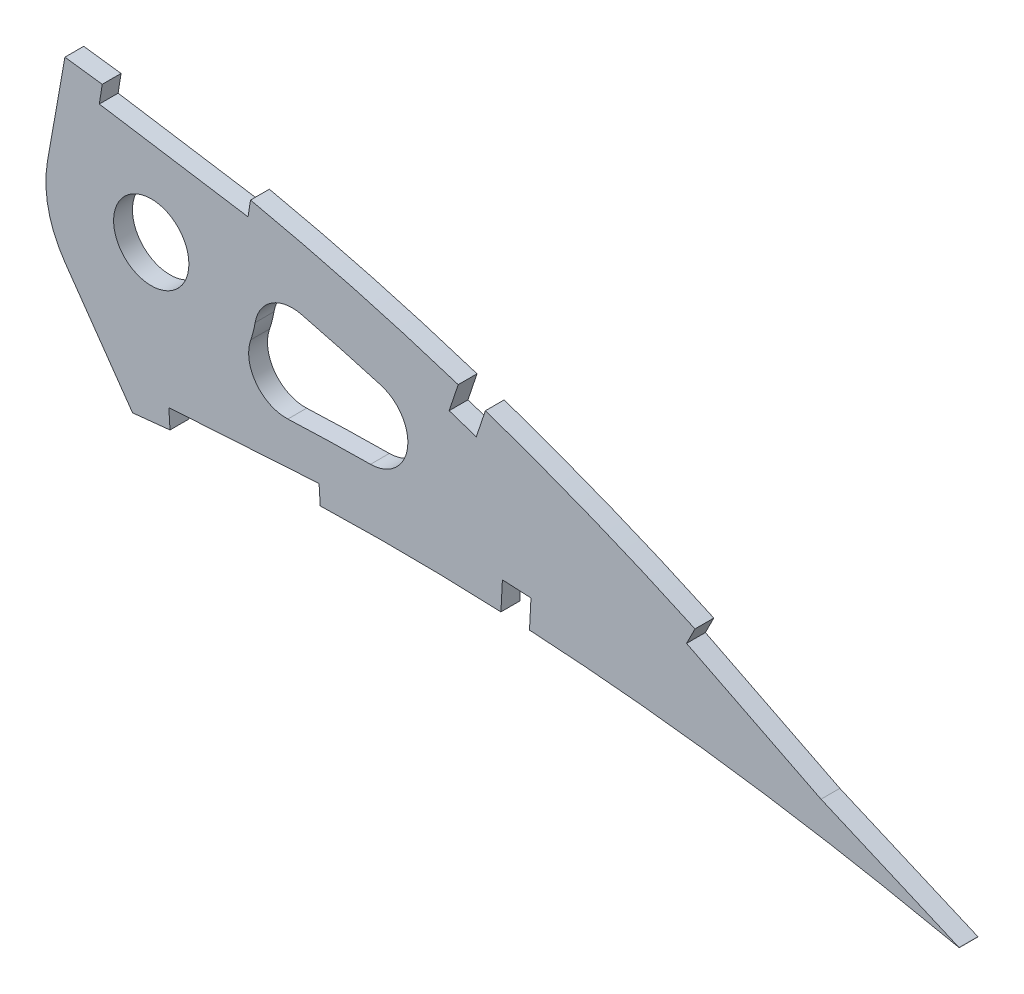
SolidWorks part; units mm, degrees
material "Pine"
ref_plane "Front Plane" through (0, 0, 0) normal (0, 0, 1) x (1, 0, 0)
ref_plane "Top Plane" through (0, 0, 0) normal (0, 1, 0) x (1, 0, 0)
ref_plane "Right Plane" through (0, 0, 0) normal (1, 0, 0) x (0, 0, -1)
curve "Curve1"
  spline degree 3 poles (0, 0, 0) (0.1249, -0.5894, 0) (0.3751, -1.7709, 0) (1.0551, -3.4717, 0) (1.9543, -5.1067, 0) (3.0917, -6.6716, 0) (4.4597, -8.1658, 0) (6.0551, -9.5909, 0) (7.8766, -10.9463, 0) (9.9217, -12.2312, 0) (12.1874, -13.447, 0) (14.6712, -14.593, 0) (17.3708, -15.6688, 0) (20.2833, -16.6729, 0) (23.4051, -17.607, 0) (26.7332, -18.4687, 0) (30.2639, -19.2592, 0) (33.9938, -19.9766, 0) (37.9188, -20.6214, 0) (42.0348, -21.1935, 0) (46.3376, -21.6931, 0) (50.823, -22.1192, 0) (55.4866, -22.4726, 0) (60.3236, -22.7538, 0) (65.3294, -22.9634, 0) (70.4993, -23.1008, 0) (75.828, -23.1681, 0) (81.3109, -23.1662, 0) (86.9426, -23.0948, 0) (92.7182, -22.9577, 0) (98.6323, -22.754, 0) (104.6794, -22.4863, 0) (110.8541, -22.1572, 0) (117.1509, -21.7679, 0) (123.5642, -21.32, 0) (130.0885, -20.8172, 0) (136.7178, -20.2607, 0) (143.4464, -19.6538, 0) (150.2683, -18.9994, 0) (157.1776, -18.2998, 0) (164.1682, -17.5581, 0) (171.2339, -16.7767, 0) (178.3687, -15.9599, 0) (185.566, -15.1091, 0) (192.8198, -14.2292, 0) (200.1233, -13.3218, 0) (207.4703, -12.3905, 0) (214.8542, -11.4396, 0) (222.2681, -10.469, 0) (229.7058, -9.4856, 0) (237.1601, -8.4887, 0) (244.6246, -7.4833, 0) (252.0922, -6.4726, 0) (259.5558, -5.4569, 0) (267.0088, -4.4404, 0) (274.4442, -3.4259, 0) (281.8548, -2.4135, 0) (289.2339, -1.4081, 0) (296.574, -0.4098, 0) (303.8684, 0.5795, 0) (311.1101, 1.5569, 0) (318.2922, 2.521, 0) (325.4074, 3.4714, 0) (332.4485, 4.4082, 0) (339.3029, 5.3032, 0) (345.9529, 6.204, 0) (352.4207, 6.9424, 0) (358.808, 7.5727, 0) (365.1214, 8.0894, 0) (371.3533, 8.5001, 0) (377.4966, 8.8075, 0) (383.544, 9.0161, 0) (389.4878, 9.132, 0) (395.3205, 9.1582, 0) (401.0343, 9.1029, 0) (406.6218, 8.9708, 0) (412.075, 8.7675, 0) (417.3864, 8.5002, 0) (422.5485, 8.1759, 0) (427.5535, 7.7996, 0) (432.3944, 7.38, 0) (437.0637, 6.9232, 0) (441.5544, 6.4344, 0) (445.8598, 5.924, 0) (449.973, 5.3952, 0) (453.8879, 4.8568, 0) (457.5982, 4.3142, 0) (461.0979, 3.7743, 0) (464.3817, 3.2423, 0) (467.4441, 2.7253, 0) (470.2803, 2.228, 0) (472.8856, 1.7553, 0) (475.2562, 1.3133, 0) (477.3874, 0.904, 0) (479.2765, 0.5343, 0) (480.9199, 0.2058, 0) (482.3151, -0.077, 0) (483.4599, -0.3128, 0) (484.3523, -0.4979, 0) (484.9907, -0.6325, 0) (485.3743, -0.7125, 0) (485.5448, -0.7489, 0) (485.5874, -0.758, 0) knots 0 0 0 0 0.003638 0.007293 0.011028 0.014901 0.018963 0.023258 0.027821 0.032679 0.037853 0.043362 0.049215 0.055422 0.061989 0.068918 0.076211 0.083868 0.091887 0.100266 0.109 0.118085 0.127515 0.137285 0.147388 0.157816 0.168563 0.179619 0.190977 0.202627 0.21456 0.226767 0.239236 0.251959 0.264924 0.27812 0.291536 0.30516 0.318981 0.332985 0.347163 0.361499 0.375981 0.390597 0.405333 0.420175 0.43511 0.450124 0.465203 0.480333 0.495501 0.51069 0.525887 0.541078 0.556247 0.571382 0.586466 0.601485 0.616424 0.631269 0.646007 0.660621 0.675098 0.689423 0.703582 0.716908 0.730009 0.742952 0.755726 0.76832 0.780724 0.792927 0.804916 0.816679 0.828204 0.839475 0.850481 0.861208 0.871639 0.881763 0.891564 0.901027 0.910139 0.918884 0.927249 0.935221 0.942785 0.949928 0.956638 0.962904 0.968712 0.974054 0.978918 0.983297 0.98718 0.990561 0.993433 0.995791 0.99763 0.998946 0.999737 1 1 1 1
curve "Curve2"
  spline degree 3 poles (486.1938, 0.758, 0) (486.1565, 0.781, 0) (486.0077, 0.8729, 0) (485.6723, 1.0786, 0) (485.1139, 1.4213, 0) (484.3321, 1.8984, 0) (483.3276, 2.5088, 0) (482.0999, 3.2482, 0) (480.6498, 4.1141, 0) (478.9775, 5.1026, 0) (477.0833, 6.2089, 0) (474.9678, 7.4286, 0) (472.6313, 8.7548, 0) (470.0748, 10.182, 0) (467.2989, 11.7035, 0) (464.3043, 13.3123, 0) (461.0921, 15.0004, 0) (457.6635, 16.7605, 0) (454.019, 18.5827, 0) (450.1605, 20.4596, 0) (446.0892, 22.3819, 0) (441.8065, 24.3391, 0) (437.3149, 26.3234, 0) (432.6155, 28.3224, 0) (427.7112, 30.3274, 0) (422.6039, 32.3272, 0) (417.2967, 34.3124, 0) (411.7916, 36.2703, 0) (406.0928, 38.1924, 0) (400.203, 40.0661, 0) (394.1264, 41.8812, 0) (387.8666, 43.626, 0) (381.4288, 45.2916, 0) (374.8171, 46.8658, 0) (368.037, 48.3381, 0) (361.0939, 49.6996, 0) (353.9938, 50.9366, 0) (346.7562, 52.0484, 0) (339.4976, 52.9732, 0) (332.2539, 53.8802, 0) (325.021, 54.7322, 0) (317.6998, 55.5482, 0) (310.2971, 56.3235, 0) (302.8205, 57.0556, 0) (295.2774, 57.7415, 0) (287.6757, 58.3791, 0) (280.0227, 58.9648, 0) (272.3266, 59.4977, 0) (264.5949, 59.9731, 0) (256.8359, 60.3907, 0) (249.0573, 60.7475, 0) (241.2675, 61.0411, 0) (233.4745, 61.2698, 0) (225.6865, 61.4312, 0) (217.912, 61.5245, 0) (210.159, 61.547, 0) (202.4359, 61.4984, 0) (194.7508, 61.377, 0) (187.1122, 61.1811, 0) (179.5282, 60.9103, 0) (172.0069, 60.5649, 0) (164.5567, 60.1418, 0) (157.1855, 59.6438, 0) (149.9016, 59.0688, 0) (142.713, 58.4167, 0) (135.6273, 57.6901, 0) (128.6522, 56.887, 0) (121.7954, 56.0099, 0) (115.0642, 55.0603, 0) (108.4663, 54.0378, 0) (102.0087, 52.9453, 0) (95.6983, 51.784, 0) (89.542, 50.5572, 0) (83.5463, 49.2652, 0) (77.7176, 47.912, 0) (72.062, 46.4999, 0) (66.5855, 45.0315, 0) (61.2937, 43.5103, 0) (56.192, 41.9397, 0) (51.2862, 40.3215, 0) (46.5802, 38.6618, 0) (42.0796, 36.9619, 0) (37.788, 35.2268, 0) (33.7103, 33.4591, 0) (29.8497, 31.6641, 0) (26.2104, 29.8437, 0) (22.7951, 28.0033, 0) (19.6072, 26.1454, 0) (16.6497, 24.2737, 0) (13.924, 22.3929, 0) (11.4337, 20.504, 0) (9.1798, 18.612, 0) (7.1636, 16.7197, 0) (5.388, 14.8284, 0) (3.8531, 12.9414, 0) (2.5606, 11.0602, 0) (1.511, 9.1866, 0) (0.7066, 7.3219, 0) (0.1466, 5.4673, 0) (-0.16, 3.6254, 0) (-0.2363, 1.7948, 0) (-0.0786, 0.5974, 0) (0, 0, 0) knots 0 0 0 0 0.000254 0.001015 0.002283 0.004057 0.006331 0.009105 0.012374 0.016134 0.02038 0.025106 0.030306 0.035972 0.0421 0.048678 0.055702 0.06316 0.071046 0.07935 0.088063 0.097176 0.106678 0.116562 0.126814 0.137428 0.148394 0.1597 0.171338 0.183298 0.19557 0.208144 0.221012 0.234162 0.247587 0.261277 0.275223 0.289414 0.303771 0.317689 0.331784 0.34604 0.360444 0.374983 0.38964 0.404403 0.419257 0.434187 0.449177 0.464215 0.479284 0.49437 0.509458 0.524532 0.539579 0.554583 0.56953 0.584403 0.599191 0.613877 0.628447 0.642889 0.657186 0.671326 0.685294 0.699078 0.712665 0.726043 0.739198 0.752118 0.764792 0.777208 0.789356 0.801224 0.812804 0.824083 0.835055 0.84571 0.856038 0.866034 0.875689 0.884998 0.893953 0.902553 0.910789 0.918661 0.926166 0.933303 0.940071 0.946475 0.952518 0.958205 0.963547 0.968557 0.97325 0.977651 0.981787 0.985694 0.989415 0.993001 0.996508 1 1 1 1
sketch "Sketch1" plane through (0, 0, 0) normal (0, 0, 1) x (1, 0, 0)
  line L10 (485.5874, -0.758) -> (490.1477, -1.6846)
  line L24 (486.1938, 0.758) -> (490.1477, -1.6846)
  spline S2 degree 3 poles (-3866.8103, -1018.8258) (79.7559, 75.3438) (-9.1933, 22.1629) (1.0551, -3.4717) (1.9543, -5.1067) (3.0917, -6.6716) (4.4597, -8.1658) (6.0551, -9.5909) (7.8766, -10.9463) (9.9217, -12.2312) (12.1874, -13.447) (14.6712, -14.593) (17.3708, -15.6688) (20.2833, -16.6729) (23.4051, -17.607) (26.7332, -18.4687) (30.2639, -19.2592) (33.9938, -19.9766) (37.9188, -20.6214) (42.0348, -21.1935) (46.3376, -21.6931) (50.823, -22.1192) (55.4866, -22.4726) (60.3236, -22.7538) (65.3294, -22.9634) (70.4993, -23.1008) (75.828, -23.1681) (81.3109, -23.1662) (86.9426, -23.0948) (92.7182, -22.9577) (98.6323, -22.754) (104.6794, -22.4863) (110.8541, -22.1572) (117.1509, -21.7679) (123.5642, -21.32) (130.0885, -20.8172) (136.7178, -20.2607) (143.4464, -19.6538) (150.2683, -18.9994) (157.1776, -18.2998) (164.1682, -17.5581) (171.2339, -16.7767) (178.3687, -15.9599) (185.566, -15.1091) (192.8198, -14.2292) (200.1233, -13.3218) (207.4703, -12.3905) (214.8542, -11.4396) (222.2681, -10.469) (229.7058, -9.4856) (237.1601, -8.4887) (244.6246, -7.4833) (252.0922, -6.4726) (259.5558, -5.4569) (267.0088, -4.4404) (274.4442, -3.4259) (281.8548, -2.4135) (289.2339, -1.4081) (296.574, -0.4098) (303.8684, 0.5795) (311.1101, 1.5569) (318.2922, 2.521) (325.4074, 3.4714) (332.4485, 4.4082) (339.3029, 5.3032) (345.9529, 6.204) (352.4207, 6.9424) (358.808, 7.5727) (365.1214, 8.0894) (371.3533, 8.5001) (377.4966, 8.8075) (383.544, 9.0161) (389.4878, 9.132) (395.3205, 9.1582) (401.0343, 9.1029) (406.6218, 8.9708) (412.075, 8.7675) (417.3864, 8.5002) (422.5485, 8.1759) (427.5535, 7.7996) (432.3944, 7.38) (437.0637, 6.9232) (441.5544, 6.4344) (445.8598, 5.924) (449.973, 5.3952) (453.8879, 4.8568) (457.5982, 4.3142) (461.0979, 3.7743) (464.3817, 3.2423) (467.4441, 2.7253) (470.2803, 2.228) (472.8856, 1.7553) (475.2562, 1.3133) (477.3874, 0.904) (479.2765, 0.5343) (480.9199, 0.2058) (482.3151, -0.077) (483.4599, -0.3128) (484.3523, -0.4979) (484.9907, -0.6325) (504.0158, -4.6034) (520.901, -17.6411) (1368.8084, 3899.3631) knots -0.155184 -0.155184 -0.155184 -0.155184 0.003638 0.007293 0.011028 0.014901 0.018963 0.023258 0.027821 0.032679 0.037853 0.043362 0.049215 0.055422 0.061989 0.068918 0.076211 0.083868 0.091887 0.100266 0.109 0.118085 0.127515 0.137285 0.147388 0.157816 0.168563 0.179619 0.190977 0.202627 0.21456 0.226767 0.239236 0.251959 0.264924 0.27812 0.291536 0.30516 0.318981 0.332985 0.347163 0.361499 0.375981 0.390597 0.405333 0.420175 0.43511 0.450124 0.465203 0.480333 0.495501 0.51069 0.525887 0.541078 0.556247 0.571382 0.586466 0.601485 0.616424 0.631269 0.646007 0.660621 0.675098 0.689423 0.703582 0.716908 0.730009 0.742952 0.755726 0.76832 0.780724 0.792927 0.804916 0.816679 0.828204 0.839475 0.850481 0.861208 0.871639 0.881763 0.891564 0.901027 0.910139 0.918884 0.927249 0.935221 0.942785 0.949928 0.956638 0.962904 0.968712 0.974054 0.978918 0.983297 0.98718 0.990561 0.993433 0.995791 0.99763 0.998946 0.999737 1.115177 1.115177 1.115177 1.115177 only from (0, 0) to (485.5874, -0.758) construction
  spline S3 degree 3 poles (2637.6242, 3371.1949) (518.0891, -28.6046) (504.1645, -10.2642) (485.6723, 1.0786) (485.1139, 1.4213) (484.3321, 1.8984) (483.3276, 2.5088) (482.0999, 3.2482) (480.6498, 4.1141) (478.9775, 5.1026) (477.0833, 6.2089) (474.9678, 7.4286) (472.6313, 8.7548) (470.0748, 10.182) (467.2989, 11.7035) (464.3043, 13.3123) (461.0921, 15.0004) (457.6635, 16.7605) (454.019, 18.5827) (450.1605, 20.4596) (446.0892, 22.3819) (441.8065, 24.3391) (437.3149, 26.3234) (432.6155, 28.3224) (427.7112, 30.3274) (422.6039, 32.3272) (417.2967, 34.3124) (411.7916, 36.2703) (406.0928, 38.1924) (400.203, 40.0661) (394.1264, 41.8812) (387.8666, 43.626) (381.4288, 45.2916) (374.8171, 46.8658) (368.037, 48.3381) (361.0939, 49.6996) (353.9938, 50.9366) (346.7562, 52.0484) (339.4976, 52.9732) (332.2539, 53.8802) (325.021, 54.7322) (317.6998, 55.5482) (310.2971, 56.3235) (302.8205, 57.0556) (295.2774, 57.7415) (287.6757, 58.3791) (280.0227, 58.9648) (272.3266, 59.4977) (264.5949, 59.9731) (256.8359, 60.3907) (249.0573, 60.7475) (241.2675, 61.0411) (233.4745, 61.2698) (225.6865, 61.4312) (217.912, 61.5245) (210.159, 61.547) (202.4359, 61.4984) (194.7508, 61.377) (187.1122, 61.1811) (179.5282, 60.9103) (172.0069, 60.5649) (164.5567, 60.1418) (157.1855, 59.6438) (149.9016, 59.0688) (142.713, 58.4167) (135.6273, 57.6901) (128.6522, 56.887) (121.7954, 56.0099) (115.0642, 55.0603) (108.4663, 54.0378) (102.0087, 52.9453) (95.6983, 51.784) (89.542, 50.5572) (83.5463, 49.2652) (77.7176, 47.912) (72.062, 46.4999) (66.5855, 45.0315) (61.2937, 43.5103) (56.192, 41.9397) (51.2862, 40.3215) (46.5802, 38.6618) (42.0796, 36.9619) (37.788, 35.2268) (33.7103, 33.4591) (29.8497, 31.6641) (26.2104, 29.8437) (22.7951, 28.0033) (19.6072, 26.1454) (16.6497, 24.2737) (13.924, 22.3929) (11.4337, 20.504) (9.1798, 18.612) (7.1636, 16.7197) (5.388, 14.8284) (3.8531, 12.9414) (2.5606, 11.0602) (1.511, 9.1866) (0.7066, 7.3219) (0.1466, 5.4673) (-0.16, 3.6254) (-1.3078, -23.9112) (100.477, -44.4073) (-3985.5392, -325.5751) knots -0.123624 -0.123624 -0.123624 -0.123624 0.000254 0.001015 0.002283 0.004057 0.006331 0.009105 0.012374 0.016134 0.02038 0.025106 0.030306 0.035972 0.0421 0.048678 0.055702 0.06316 0.071046 0.07935 0.088063 0.097176 0.106678 0.116562 0.126814 0.137428 0.148394 0.1597 0.171338 0.183298 0.19557 0.208144 0.221012 0.234162 0.247587 0.261277 0.275223 0.289414 0.303771 0.317689 0.331784 0.34604 0.360444 0.374983 0.38964 0.404403 0.419257 0.434187 0.449177 0.464215 0.479284 0.49437 0.509458 0.524532 0.539579 0.554583 0.56953 0.584403 0.599191 0.613877 0.628447 0.642889 0.657186 0.671326 0.685294 0.699078 0.712665 0.726043 0.739198 0.752118 0.764792 0.777208 0.789356 0.801224 0.812804 0.824083 0.835055 0.84571 0.856038 0.866034 0.875689 0.884998 0.893953 0.902553 0.910789 0.918661 0.926166 0.933303 0.940071 0.946475 0.952518 0.958205 0.963547 0.968557 0.97325 0.977651 0.981787 0.985694 0.989415 0.993001 0.996508 1.148636 1.148636 1.148636 1.148636 only from (486.1938, 0.758) to (0, 0) construction
  spline S4 degree 3 poles (0, 0) (0.1249, -0.5894) (0.3751, -1.7709) (1.0551, -3.4717) (1.9543, -5.1067) (3.0917, -6.6716) (4.4597, -8.1658) (6.0551, -9.5909) (7.8766, -10.9463) (9.9217, -12.2312) (12.1874, -13.447) (14.6712, -14.593) (17.3708, -15.6688) (20.2833, -16.6729) (23.4051, -17.607) (26.7332, -18.4687) (30.2639, -19.2592) (33.9938, -19.9766) (37.9188, -20.6214) (42.0348, -21.1935) (46.3376, -21.6931) (50.823, -22.1192) (55.4866, -22.4726) (60.3236, -22.7538) (65.3294, -22.9634) (70.4993, -23.1008) (75.828, -23.1681) (81.3109, -23.1662) (86.9426, -23.0948) (92.7182, -22.9577) (98.6323, -22.754) (104.6794, -22.4863) (110.8541, -22.1572) (117.1509, -21.7679) (123.5642, -21.32) (130.0885, -20.8172) (136.7178, -20.2607) (143.4464, -19.6538) (150.2683, -18.9994) (157.1776, -18.2998) (164.1682, -17.5581) (171.2339, -16.7767) (178.3687, -15.9599) (185.566, -15.1091) (192.8198, -14.2292) (200.1233, -13.3218) (207.4703, -12.3905) (214.8542, -11.4396) (222.2681, -10.469) (229.7058, -9.4856) (237.1601, -8.4887) (244.6246, -7.4833) (252.0922, -6.4726) (259.5558, -5.4569) (267.0088, -4.4404) (274.4442, -3.4259) (281.8548, -2.4135) (289.2339, -1.4081) (296.574, -0.4098) (303.8684, 0.5795) (311.1101, 1.5569) (318.2922, 2.521) (325.4074, 3.4714) (332.4485, 4.4082) (339.3029, 5.3032) (345.9529, 6.204) (352.4207, 6.9424) (358.808, 7.5727) (365.1214, 8.0894) (371.3533, 8.5001) (377.4966, 8.8075) (383.544, 9.0161) (389.4878, 9.132) (395.3205, 9.1582) (401.0343, 9.1029) (406.6218, 8.9708) (412.075, 8.7675) (417.3864, 8.5002) (422.5485, 8.1759) (427.5535, 7.7996) (432.3944, 7.38) (437.0637, 6.9232) (441.5544, 6.4344) (445.8598, 5.924) (449.973, 5.3952) (453.8879, 4.8568) (457.5982, 4.3142) (461.0979, 3.7743) (464.3817, 3.2423) (467.4441, 2.7253) (470.2803, 2.228) (472.8856, 1.7553) (475.2562, 1.3133) (477.3874, 0.904) (479.2765, 0.5343) (480.9199, 0.2058) (482.3151, -0.077) (483.4599, -0.3128) (484.3523, -0.4979) (484.9907, -0.6325) (485.3743, -0.7125) (485.5448, -0.7489) (485.5874, -0.758) knots 0 0 0 0 0.003638 0.007293 0.011028 0.014901 0.018963 0.023258 0.027821 0.032679 0.037853 0.043362 0.049215 0.055422 0.061989 0.068918 0.076211 0.083868 0.091887 0.100266 0.109 0.118085 0.127515 0.137285 0.147388 0.157816 0.168563 0.179619 0.190977 0.202627 0.21456 0.226767 0.239236 0.251959 0.264924 0.27812 0.291536 0.30516 0.318981 0.332985 0.347163 0.361499 0.375981 0.390597 0.405333 0.420175 0.43511 0.450124 0.465203 0.480333 0.495501 0.51069 0.525887 0.541078 0.556247 0.571382 0.586466 0.601485 0.616424 0.631269 0.646007 0.660621 0.675098 0.689423 0.703582 0.716908 0.730009 0.742952 0.755726 0.76832 0.780724 0.792927 0.804916 0.816679 0.828204 0.839475 0.850481 0.861208 0.871639 0.881763 0.891564 0.901027 0.910139 0.918884 0.927249 0.935221 0.942785 0.949928 0.956638 0.962904 0.968712 0.974054 0.978918 0.983297 0.98718 0.990561 0.993433 0.995791 0.99763 0.998946 0.999737 1 1 1 1
  spline S5 degree 3 poles (486.1938, 0.758) (486.1565, 0.781) (486.0077, 0.8729) (485.6723, 1.0786) (485.1139, 1.4213) (484.3321, 1.8984) (483.3276, 2.5088) (482.0999, 3.2482) (480.6498, 4.1141) (478.9775, 5.1026) (477.0833, 6.2089) (474.9678, 7.4286) (472.6313, 8.7548) (470.0748, 10.182) (467.2989, 11.7035) (464.3043, 13.3123) (461.0921, 15.0004) (457.6635, 16.7605) (454.019, 18.5827) (450.1605, 20.4596) (446.0892, 22.3819) (441.8065, 24.3391) (437.3149, 26.3234) (432.6155, 28.3224) (427.7112, 30.3274) (422.6039, 32.3272) (417.2967, 34.3124) (411.7916, 36.2703) (406.0928, 38.1924) (400.203, 40.0661) (394.1264, 41.8812) (387.8666, 43.626) (381.4288, 45.2916) (374.8171, 46.8658) (368.037, 48.3381) (361.0939, 49.6996) (353.9938, 50.9366) (346.7562, 52.0484) (339.4976, 52.9732) (332.2539, 53.8802) (325.021, 54.7322) (317.6998, 55.5482) (310.2971, 56.3235) (302.8205, 57.0556) (295.2774, 57.7415) (287.6757, 58.3791) (280.0227, 58.9648) (272.3266, 59.4977) (264.5949, 59.9731) (256.8359, 60.3907) (249.0573, 60.7475) (241.2675, 61.0411) (233.4745, 61.2698) (225.6865, 61.4312) (217.912, 61.5245) (210.159, 61.547) (202.4359, 61.4984) (194.7508, 61.377) (187.1122, 61.1811) (179.5282, 60.9103) (172.0069, 60.5649) (164.5567, 60.1418) (157.1855, 59.6438) (149.9016, 59.0688) (142.713, 58.4167) (135.6273, 57.6901) (128.6522, 56.887) (121.7954, 56.0099) (115.0642, 55.0603) (108.4663, 54.0378) (102.0087, 52.9453) (95.6983, 51.784) (89.542, 50.5572) (83.5463, 49.2652) (77.7176, 47.912) (72.062, 46.4999) (66.5855, 45.0315) (61.2937, 43.5103) (56.192, 41.9397) (51.2862, 40.3215) (46.5802, 38.6618) (42.0796, 36.9619) (37.788, 35.2268) (33.7103, 33.4591) (29.8497, 31.6641) (26.2104, 29.8437) (22.7951, 28.0033) (19.6072, 26.1454) (16.6497, 24.2737) (13.924, 22.3929) (11.4337, 20.504) (9.1798, 18.612) (7.1636, 16.7197) (5.388, 14.8284) (3.8531, 12.9414) (2.5606, 11.0602) (1.511, 9.1866) (0.7066, 7.3219) (0.1466, 5.4673) (-0.16, 3.6254) (-0.2363, 1.7948) (-0.0786, 0.5974) (0, 0) knots 0 0 0 0 0.000254 0.001015 0.002283 0.004057 0.006331 0.009105 0.012374 0.016134 0.02038 0.025106 0.030306 0.035972 0.0421 0.048678 0.055702 0.06316 0.071046 0.07935 0.088063 0.097176 0.106678 0.116562 0.126814 0.137428 0.148394 0.1597 0.171338 0.183298 0.19557 0.208144 0.221012 0.234162 0.247587 0.261277 0.275223 0.289414 0.303771 0.317689 0.331784 0.34604 0.360444 0.374983 0.38964 0.404403 0.419257 0.434187 0.449177 0.464215 0.479284 0.49437 0.509458 0.524532 0.539579 0.554583 0.56953 0.584403 0.599191 0.613877 0.628447 0.642889 0.657186 0.671326 0.685294 0.699078 0.712665 0.726043 0.739198 0.752118 0.764792 0.777208 0.789356 0.801224 0.812804 0.824083 0.835055 0.84571 0.856038 0.866034 0.875689 0.884998 0.893953 0.902553 0.910789 0.918661 0.926166 0.933303 0.940071 0.946475 0.952518 0.958205 0.963547 0.968557 0.97325 0.977651 0.981787 0.985694 0.989415 0.993001 0.996508 1 1 1 1
extrude "Boss-Extrude1" add sketch "Sketch1" along normal blind 3.175
sketch "Sketch5" plane through (0, 0, 3.175) normal (0, 0, 1) x (1, 0, 0)
  line L0 (336.323, 36.32) -> (339.2642, 53)
  line L1 (339.2684, 23.0344) -> (350.6801, 6.7368)
  line L2 (353.8329, 33.2326) -> (374.466, 33.2326)
  circle A0 centre (353.8329, 33.2326) radius 6.35
  circle A1 centre (353.8329, 33.2326) radius 6.35
  circle A2 centre (353.8329, 33.2326) radius 17.78
  spline S0 degree 3 poles (-1939.0794, -487.5307) (48.5631, 55.4905) (-7.2206, 17.2286) (1.0551, -3.4717) (1.9543, -5.1067) (3.0917, -6.6716) (4.4597, -8.1658) (6.0551, -9.5909) (7.8766, -10.9463) (9.9217, -12.2312) (12.1874, -13.447) (14.6712, -14.593) (17.3708, -15.6688) (20.2833, -16.6729) (23.4051, -17.607) (26.7332, -18.4687) (30.2639, -19.2592) (33.9938, -19.9766) (37.9188, -20.6214) (42.0348, -21.1935) (46.3376, -21.6931) (50.823, -22.1192) (55.4866, -22.4726) (60.3236, -22.7538) (65.3294, -22.9634) (70.4993, -23.1008) (75.828, -23.1681) (81.3109, -23.1662) (86.9426, -23.0948) (92.7182, -22.9577) (98.6323, -22.754) (104.6794, -22.4863) (110.8541, -22.1572) (117.1509, -21.7679) (123.5642, -21.32) (130.0885, -20.8172) (136.7178, -20.2607) (143.4464, -19.6538) (150.2683, -18.9994) (157.1776, -18.2998) (164.1682, -17.5581) (171.2339, -16.7767) (178.3687, -15.9599) (185.566, -15.1091) (192.8198, -14.2292) (200.1233, -13.3218) (207.4703, -12.3905) (214.8542, -11.4396) (222.2681, -10.469) (229.7058, -9.4856) (237.1601, -8.4887) (244.6246, -7.4833) (252.0922, -6.4726) (259.5558, -5.4569) (267.0088, -4.4404) (274.4442, -3.4259) (281.8548, -2.4135) (289.2339, -1.4081) (296.574, -0.4098) (303.8684, 0.5795) (311.1101, 1.5569) (318.2922, 2.521) (325.4074, 3.4714) (332.4485, 4.4082) (339.3029, 5.3032) (345.9529, 6.204) (352.4207, 6.9424) (358.808, 7.5727) (365.1214, 8.0894) (371.3533, 8.5001) (377.4966, 8.8075) (383.544, 9.0161) (389.4878, 9.132) (395.3205, 9.1582) (401.0343, 9.1029) (406.6218, 8.9708) (412.075, 8.7675) (417.3864, 8.5002) (422.5485, 8.1759) (427.5535, 7.7996) (432.3944, 7.38) (437.0637, 6.9232) (441.5544, 6.4344) (445.8598, 5.924) (449.973, 5.3952) (453.8879, 4.8568) (457.5982, 4.3142) (461.0979, 3.7743) (464.3817, 3.2423) (467.4441, 2.7253) (470.2803, 2.228) (472.8856, 1.7553) (475.2562, 1.3133) (477.3874, 0.904) (479.2765, 0.5343) (480.9199, 0.2058) (482.3151, -0.077) (483.4599, -0.3128) (484.3523, -0.4979) (484.9907, -0.6325) (500.1693, -3.8005) (513.9154, -12.6904) (943.5402, 1945.4943) knots -0.123191 -0.123191 -0.123191 -0.123191 0.003638 0.007293 0.011028 0.014901 0.018963 0.023258 0.027821 0.032679 0.037853 0.043362 0.049215 0.055422 0.061989 0.068918 0.076211 0.083868 0.091887 0.100266 0.109 0.118085 0.127515 0.137285 0.147388 0.157816 0.168563 0.179619 0.190977 0.202627 0.21456 0.226767 0.239236 0.251959 0.264924 0.27812 0.291536 0.30516 0.318981 0.332985 0.347163 0.361499 0.375981 0.390597 0.405333 0.420175 0.43511 0.450124 0.465203 0.480333 0.495501 0.51069 0.525887 0.541078 0.556247 0.571382 0.586466 0.601485 0.616424 0.631269 0.646007 0.660621 0.675098 0.689423 0.703582 0.716908 0.730009 0.742952 0.755726 0.76832 0.780724 0.792927 0.804916 0.816679 0.828204 0.839475 0.850481 0.861208 0.871639 0.881763 0.891564 0.901027 0.910139 0.918884 0.927249 0.935221 0.942785 0.949928 0.956638 0.962904 0.968712 0.974054 0.978918 0.983297 0.98718 0.990561 0.993433 0.995791 0.99763 0.998946 0.999737 1.091411 1.091411 1.091411 1.091411 only from (0, 0) to (485.5874, -0.758) construction
  spline S1 degree 3 poles (1577.8242, 1676.0308) (512.2068, -21.3963) (500.4185, -7.9664) (485.6723, 1.0786) (485.1139, 1.4213) (484.3321, 1.8984) (483.3276, 2.5088) (482.0999, 3.2482) (480.6498, 4.1141) (478.9775, 5.1026) (477.0833, 6.2089) (474.9678, 7.4286) (472.6313, 8.7548) (470.0748, 10.182) (467.2989, 11.7035) (464.3043, 13.3123) (461.0921, 15.0004) (457.6635, 16.7605) (454.019, 18.5827) (450.1605, 20.4596) (446.0892, 22.3819) (441.8065, 24.3391) (437.3149, 26.3234) (432.6155, 28.3224) (427.7112, 30.3274) (422.6039, 32.3272) (417.2967, 34.3124) (411.7916, 36.2703) (406.0928, 38.1924) (400.203, 40.0661) (394.1264, 41.8812) (387.8666, 43.626) (381.4288, 45.2916) (374.8171, 46.8658) (368.037, 48.3381) (361.0939, 49.6996) (353.9938, 50.9366) (346.7562, 52.0484) (339.4976, 52.9732) (332.2539, 53.8802) (325.021, 54.7322) (317.6998, 55.5482) (310.2971, 56.3235) (302.8205, 57.0556) (295.2774, 57.7415) (287.6757, 58.3791) (280.0227, 58.9648) (272.3266, 59.4977) (264.5949, 59.9731) (256.8359, 60.3907) (249.0573, 60.7475) (241.2675, 61.0411) (233.4745, 61.2698) (225.6865, 61.4312) (217.912, 61.5245) (210.159, 61.547) (202.4359, 61.4984) (194.7508, 61.377) (187.1122, 61.1811) (179.5282, 60.9103) (172.0069, 60.5649) (164.5567, 60.1418) (157.1855, 59.6438) (149.9016, 59.0688) (142.713, 58.4167) (135.6273, 57.6901) (128.6522, 56.887) (121.7954, 56.0099) (115.0642, 55.0603) (108.4663, 54.0378) (102.0087, 52.9453) (95.6983, 51.784) (89.542, 50.5572) (83.5463, 49.2652) (77.7176, 47.912) (72.062, 46.4999) (66.5855, 45.0315) (61.2937, 43.5103) (56.192, 41.9397) (51.2862, 40.3215) (46.5802, 38.6618) (42.0796, 36.9619) (37.788, 35.2268) (33.7103, 33.4591) (29.8497, 31.6641) (26.2104, 29.8437) (22.7951, 28.0033) (19.6072, 26.1454) (16.6497, 24.2737) (13.924, 22.3929) (11.4337, 20.504) (9.1798, 18.612) (7.1636, 16.7197) (5.388, 14.8284) (3.8531, 12.9414) (2.5606, 11.0602) (1.511, 9.1866) (0.7066, 7.3219) (0.1466, 5.4673) (-0.16, 3.6254) (-1.0869, -18.6116) (64.385, -36.0874) (-1990.8444, -185.2686) knots -0.098119 -0.098119 -0.098119 -0.098119 0.000254 0.001015 0.002283 0.004057 0.006331 0.009105 0.012374 0.016134 0.02038 0.025106 0.030306 0.035972 0.0421 0.048678 0.055702 0.06316 0.071046 0.07935 0.088063 0.097176 0.106678 0.116562 0.126814 0.137428 0.148394 0.1597 0.171338 0.183298 0.19557 0.208144 0.221012 0.234162 0.247587 0.261277 0.275223 0.289414 0.303771 0.317689 0.331784 0.34604 0.360444 0.374983 0.38964 0.404403 0.419257 0.434187 0.449177 0.464215 0.479284 0.49437 0.509458 0.524532 0.539579 0.554583 0.56953 0.584403 0.599191 0.613877 0.628447 0.642889 0.657186 0.671326 0.685294 0.699078 0.712665 0.726043 0.739198 0.752118 0.764792 0.777208 0.789356 0.801224 0.812804 0.824083 0.835055 0.84571 0.856038 0.866034 0.875689 0.884998 0.893953 0.902553 0.910789 0.918661 0.926166 0.933303 0.940071 0.946475 0.952518 0.958205 0.963547 0.968557 0.97325 0.977651 0.981787 0.985694 0.989415 0.993001 0.996508 1.117993 1.117993 1.117993 1.117993 only from (486.1938, 0.758) to (0, 0) construction
  spline S2 degree 3 poles (0, 0) (0.1249, -0.5894) (0.3751, -1.7709) (1.0551, -3.4717) (1.9543, -5.1067) (3.0917, -6.6716) (4.4597, -8.1658) (6.0551, -9.5909) (7.8766, -10.9463) (9.9217, -12.2312) (12.1874, -13.447) (14.6712, -14.593) (17.3708, -15.6688) (20.2833, -16.6729) (23.4051, -17.607) (26.7332, -18.4687) (30.2639, -19.2592) (33.9938, -19.9766) (37.9188, -20.6214) (42.0348, -21.1935) (46.3376, -21.6931) (50.823, -22.1192) (55.4866, -22.4726) (60.3236, -22.7538) (65.3294, -22.9634) (70.4993, -23.1008) (75.828, -23.1681) (81.3109, -23.1662) (86.9426, -23.0948) (92.7182, -22.9577) (98.6323, -22.754) (104.6794, -22.4863) (110.8541, -22.1572) (117.1509, -21.7679) (123.5642, -21.32) (130.0885, -20.8172) (136.7178, -20.2607) (143.4464, -19.6538) (150.2683, -18.9994) (157.1776, -18.2998) (164.1682, -17.5581) (171.2339, -16.7767) (178.3687, -15.9599) (185.566, -15.1091) (192.8198, -14.2292) (200.1233, -13.3218) (207.4703, -12.3905) (214.8542, -11.4396) (222.2681, -10.469) (229.7058, -9.4856) (237.1601, -8.4887) (244.6246, -7.4833) (252.0922, -6.4726) (259.5558, -5.4569) (267.0088, -4.4404) (274.4442, -3.4259) (281.8548, -2.4135) (289.2339, -1.4081) (296.574, -0.4098) (303.8684, 0.5795) (311.1101, 1.5569) (318.2922, 2.521) (325.4074, 3.4714) (332.4485, 4.4082) (339.3029, 5.3032) (345.9529, 6.204) (352.4207, 6.9424) (358.808, 7.5727) (365.1214, 8.0894) (371.3533, 8.5001) (377.4966, 8.8075) (383.544, 9.0161) (389.4878, 9.132) (395.3205, 9.1582) (401.0343, 9.1029) (406.6218, 8.9708) (412.075, 8.7675) (417.3864, 8.5002) (422.5485, 8.1759) (427.5535, 7.7996) (432.3944, 7.38) (437.0637, 6.9232) (441.5544, 6.4344) (445.8598, 5.924) (449.973, 5.3952) (453.8879, 4.8568) (457.5982, 4.3142) (461.0979, 3.7743) (464.3817, 3.2423) (467.4441, 2.7253) (470.2803, 2.228) (472.8856, 1.7553) (475.2562, 1.3133) (477.3874, 0.904) (479.2765, 0.5343) (480.9199, 0.2058) (482.3151, -0.077) (483.4599, -0.3128) (484.3523, -0.4979) (484.9907, -0.6325) (485.3743, -0.7125) (485.5448, -0.7489) (485.5874, -0.758) knots 0 0 0 0 0.003638 0.007293 0.011028 0.014901 0.018963 0.023258 0.027821 0.032679 0.037853 0.043362 0.049215 0.055422 0.061989 0.068918 0.076211 0.083868 0.091887 0.100266 0.109 0.118085 0.127515 0.137285 0.147388 0.157816 0.168563 0.179619 0.190977 0.202627 0.21456 0.226767 0.239236 0.251959 0.264924 0.27812 0.291536 0.30516 0.318981 0.332985 0.347163 0.361499 0.375981 0.390597 0.405333 0.420175 0.43511 0.450124 0.465203 0.480333 0.495501 0.51069 0.525887 0.541078 0.556247 0.571382 0.586466 0.601485 0.616424 0.631269 0.646007 0.660621 0.675098 0.689423 0.703582 0.716908 0.730009 0.742952 0.755726 0.76832 0.780724 0.792927 0.804916 0.816679 0.828204 0.839475 0.850481 0.861208 0.871639 0.881763 0.891564 0.901027 0.910139 0.918884 0.927249 0.935221 0.942785 0.949928 0.956638 0.962904 0.968712 0.974054 0.978918 0.983297 0.98718 0.990561 0.993433 0.995791 0.99763 0.998946 0.999737 1 1 1 1
  spline S3 degree 3 poles (486.1938, 0.758) (486.1565, 0.781) (486.0077, 0.8729) (485.6723, 1.0786) (485.1139, 1.4213) (484.3321, 1.8984) (483.3276, 2.5088) (482.0999, 3.2482) (480.6498, 4.1141) (478.9775, 5.1026) (477.0833, 6.2089) (474.9678, 7.4286) (472.6313, 8.7548) (470.0748, 10.182) (467.2989, 11.7035) (464.3043, 13.3123) (461.0921, 15.0004) (457.6635, 16.7605) (454.019, 18.5827) (450.1605, 20.4596) (446.0892, 22.3819) (441.8065, 24.3391) (437.3149, 26.3234) (432.6155, 28.3224) (427.7112, 30.3274) (422.6039, 32.3272) (417.2967, 34.3124) (411.7916, 36.2703) (406.0928, 38.1924) (400.203, 40.0661) (394.1264, 41.8812) (387.8666, 43.626) (381.4288, 45.2916) (374.8171, 46.8658) (368.037, 48.3381) (361.0939, 49.6996) (353.9938, 50.9366) (346.7562, 52.0484) (339.4976, 52.9732) (332.2539, 53.8802) (325.021, 54.7322) (317.6998, 55.5482) (310.2971, 56.3235) (302.8205, 57.0556) (295.2774, 57.7415) (287.6757, 58.3791) (280.0227, 58.9648) (272.3266, 59.4977) (264.5949, 59.9731) (256.8359, 60.3907) (249.0573, 60.7475) (241.2675, 61.0411) (233.4745, 61.2698) (225.6865, 61.4312) (217.912, 61.5245) (210.159, 61.547) (202.4359, 61.4984) (194.7508, 61.377) (187.1122, 61.1811) (179.5282, 60.9103) (172.0069, 60.5649) (164.5567, 60.1418) (157.1855, 59.6438) (149.9016, 59.0688) (142.713, 58.4167) (135.6273, 57.6901) (128.6522, 56.887) (121.7954, 56.0099) (115.0642, 55.0603) (108.4663, 54.0378) (102.0087, 52.9453) (95.6983, 51.784) (89.542, 50.5572) (83.5463, 49.2652) (77.7176, 47.912) (72.062, 46.4999) (66.5855, 45.0315) (61.2937, 43.5103) (56.192, 41.9397) (51.2862, 40.3215) (46.5802, 38.6618) (42.0796, 36.9619) (37.788, 35.2268) (33.7103, 33.4591) (29.8497, 31.6641) (26.2104, 29.8437) (22.7951, 28.0033) (19.6072, 26.1454) (16.6497, 24.2737) (13.924, 22.3929) (11.4337, 20.504) (9.1798, 18.612) (7.1636, 16.7197) (5.388, 14.8284) (3.8531, 12.9414) (2.5606, 11.0602) (1.511, 9.1866) (0.7066, 7.3219) (0.1466, 5.4673) (-0.16, 3.6254) (-0.2363, 1.7948) (-0.0786, 0.5974) (0, 0) knots 0 0 0 0 0.000254 0.001015 0.002283 0.004057 0.006331 0.009105 0.012374 0.016134 0.02038 0.025106 0.030306 0.035972 0.0421 0.048678 0.055702 0.06316 0.071046 0.07935 0.088063 0.097176 0.106678 0.116562 0.126814 0.137428 0.148394 0.1597 0.171338 0.183298 0.19557 0.208144 0.221012 0.234162 0.247587 0.261277 0.275223 0.289414 0.303771 0.317689 0.331784 0.34604 0.360444 0.374983 0.38964 0.404403 0.419257 0.434187 0.449177 0.464215 0.479284 0.49437 0.509458 0.524532 0.539579 0.554583 0.56953 0.584403 0.599191 0.613877 0.628447 0.642889 0.657186 0.671326 0.685294 0.699078 0.712665 0.726043 0.739198 0.752118 0.764792 0.777208 0.789356 0.801224 0.812804 0.824083 0.835055 0.84571 0.856038 0.866034 0.875689 0.884998 0.893953 0.902553 0.910789 0.918661 0.926166 0.933303 0.940071 0.946475 0.952518 0.958205 0.963547 0.968557 0.97325 0.977651 0.981787 0.985694 0.989415 0.993001 0.996508 1 1 1 1
  spline S4 degree 1 poles (480.8541, -7.8857) (10.0221, 1.7185) knots 0 0 1 1 construction
  spline S5 degree 1 poles (10.0221, 1.7185) (487.707, 9.1785) knots 0 0 1 1 construction
  spline S6 degree 3 poles (480.8541, -7.8857) (480.7201, -7.8029) (480.4589, -7.6425) (479.8783, -7.2863) (478.9124, -6.6962) (476.9448, -5.5034) (473.0052, -3.1584) (465.0526, 1.417) (448.8811, 10.0668) (425.053, 20.9312) (400.3824, 29.6362) (380.244, 35.2169) (367.5068, 38.1191) (357.2621, 40.0741) (349.5101, 41.3746) (341.8335, 42.449) (333.8166, 43.4475) (325.9049, 44.4061) (315.2983, 45.6009) (296.7451, 47.4959) (270.1814, 49.6136) (238.2719, 51.1465) (206.364, 51.5674) (174.5136, 50.7436) (142.8023, 48.4874) (116.597, 45.208) (95.874, 41.5554) (80.5049, 38.2363) (65.3742, 34.2512) (53.0577, 30.2789) (43.4884, 26.6248) (36.4997, 23.6156) (29.7711, 20.3046) (23.4201, 16.6518) (17.6543, 12.6276) (13.6768, 8.9843) (11.4208, 6.112) (10.5313, 4.5112) (10.1421, 3.4379) (10.0302, 2.9559) (9.9731, 2.5067) (9.9642, 2.3114) (9.9656, 2.2504) (9.9657, 2.2359) (9.9791, 2.0811) (9.9996, 1.9002) (10.0148, 1.7763) (10.0221, 1.7185) knots 0 0 0 0 0.000976 0.001951 0.003903 0.007806 0.015611 0.031223 0.062446 0.124891 0.187337 0.21856 0.249783 0.265394 0.281006 0.296617 0.312229 0.32784 0.343451 0.374674 0.43712 0.499566 0.562011 0.624457 0.686903 0.749348 0.780571 0.811794 0.843017 0.87424 0.889851 0.905463 0.921074 0.936686 0.952297 0.967908 0.975714 0.98352 0.987423 0.991326 0.993277 0.995228 0.996204 0.99718 0.998156 0.998643 0.999131 0.999131 0.999131 0.999131
  spline S7 degree 3 poles (10.0221, 1.7185) (10.034, 1.6636) (10.0599, 1.5462) (10.0999, 1.3723) (10.1389, 1.2199) (10.1476, 1.1921) (10.1628, 1.1452) (10.2268, 0.9816) (10.4203, 0.5862) (10.6781, 0.1667) (11.3398, -0.673) (12.618, -1.867) (15.4809, -3.8036) (20.1586, -5.9835) (26.5914, -8.0226) (33.4675, -9.5952) (40.5985, -10.785) (47.8877, -11.6685) (57.7439, -12.5059) (70.2368, -13.025) (85.3646, -13.0282) (100.5676, -12.5574) (120.8957, -11.433) (146.3656, -9.2898) (176.9642, -5.9687) (207.5889, -2.1743) (238.231, 1.8884) (268.9049, 6.0711) (294.4834, 9.566) (312.4086, 11.9846) (322.6494, 13.3534) (329.0537, 14.2071) (334.1907, 14.8818) (338.0026, 15.3833) (341.8382, 15.8997) (345.8011, 16.4075) (349.7595, 16.8632) (355.0135, 17.4179) (364.2536, 18.2584) (377.4648, 19.063) (398.6452, 19.5221) (425.0949, 18.559) (451.3668, 15.6636) (469.5828, 12.7141) (478.6615, 11.0165) (482.841, 10.1846) (484.7931, 9.786) (485.7414, 9.5904) (486.586, 9.4145) (487.1818, 9.2892) (487.5367, 9.2148) (487.707, 9.1785) knots 0.000905 0.000905 0.000905 0.000905 0.001393 0.00188 0.002856 0.003832 0.004808 0.006759 0.00871 0.012613 0.016516 0.024321 0.032127 0.047737 0.063348 0.078959 0.09457 0.110181 0.125792 0.157013 0.188235 0.219457 0.250679 0.313122 0.375565 0.438009 0.500452 0.562896 0.625339 0.656561 0.672172 0.687783 0.695588 0.703394 0.711199 0.719004 0.72681 0.734615 0.750226 0.781448 0.81267 0.875113 0.937557 0.968778 0.984389 0.992195 0.994146 0.996097 0.998049 0.999024 1 1 1 1
  dimension "D1" = 35.56
  dimension "D2" = 10.16
  dimension "D3" = 80
  dimension "D4" = 55
extrude "Cut-Extrude5" cut sketch "Sketch5" against normal through all contours S7 S6 A2 L0 L1 | S6 S7 L1 A2 | A1 | A2 S7 S6 region at (173.1936, 20.4117, 3.175) region at (347.6625, 33.2326, 3.175) region at (167.5374, 53.746, 3.175) region at (390.6788, 25.1228, 3.175)
sketch "Sketch6" plane through (0, 0, 0) normal (0, 0, -1) x (-1, 0, 0)
  line L0 (-417.6503, 8.4753) -> (-417.6503, 7.6122)
  line L1 (-491.4214, 1.2315) -> (-468.1792, 11.2389)
  line L2 (-417.6503, 7.6122) -> (-412.8307, 7.8598)
  line L3 (-490.1657, -1.6847) -> (-491.4214, 1.2315)
  line L4 (-412.8307, 7.8598) -> (-412.8307, 8.7229)
  line L5 (-468.1792, 11.2389) -> (-445.5766, 22.6173)
  line L6 (-382.3474, 8.9759) -> (-382.3474, 7.8598)
  line L7 (-417.6503, 8.4753) -> (-417.8979, 13.295)
  line L8 (-382.3474, 7.8598) -> (-356.9972, 6.2903)
  line L9 (-417.8979, 13.295) -> (-413.0783, 13.5426)
  line L10 (-356.9972, 6.2903) -> (-356.9972, 7.3864)
  line L11 (-408.6744, 32.2283) -> (-410.2016, 36.8062)
  line L13 (-410.2016, 36.8062) -> (-405.6236, 38.3335)
  line L15 (-382.3474, 8.9759) -> (-382.1488, 12.1446)
  line L17 (-382.1488, 12.1446) -> (-356.7986, 10.5551)
  line L19 (-370.1628, 45.1121) -> (-370.6549, 48.2487)
  line L21 (-370.6549, 48.2487) -> (-345.562, 52.1861)
  line L23 (-466.8364, 8.3603) -> (-490.1657, -1.6847)
  line L25 (-444.149, 19.7814) -> (-466.8364, 8.3603)
  line L27 (-445.5766, 22.6173) -> (-444.149, 19.7814)
  line L31 (-413.0783, 13.5426) -> (-412.8307, 8.7229)
  line L35 (-356.7986, 10.5551) -> (-356.9972, 7.3864)
  line L37 (-404.0964, 33.7555) -> (-408.6744, 32.2283)
  line L39 (-405.6236, 38.3335) -> (-404.0964, 33.7555)
  line L41 (-345.0698, 49.0495) -> (-370.1628, 45.1121)
  line L43 (-345.562, 52.1861) -> (-345.0698, 49.0495)
extrude "Cut-Extrude6" cut sketch "Sketch6" against normal blind 7.62 body kept at (485.5874, -0.758, 0)
fillet "Fillet1" radius 6.35 3 edges at (431.7922, 17.6271, 1.5875) (363.1942, 18.1165, 1.5875) (371.1522, 37.2537, 1.5875)
